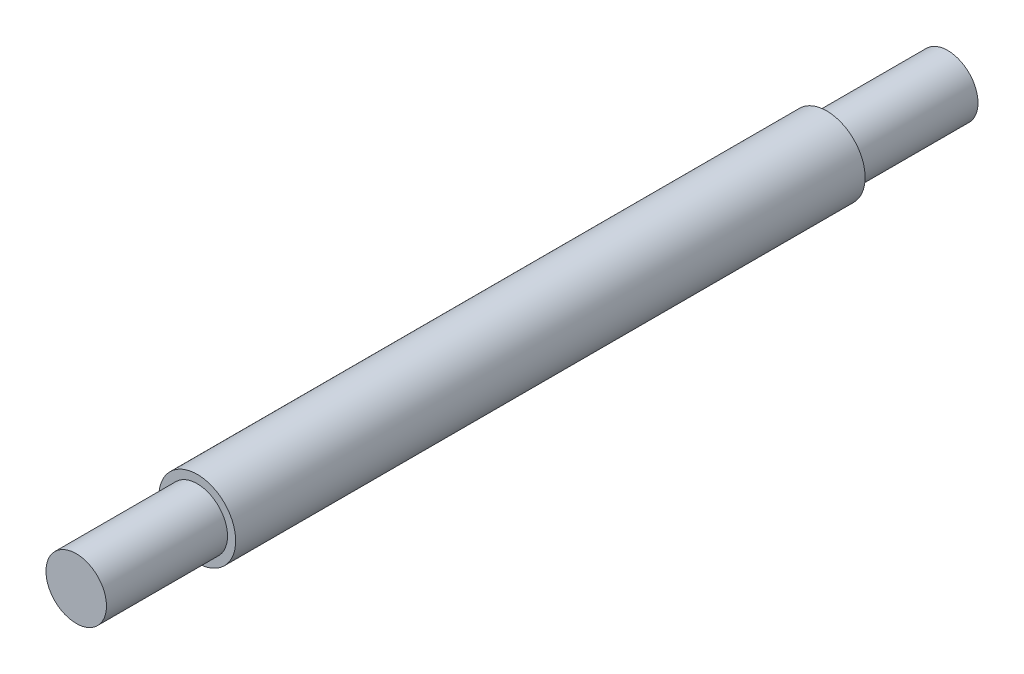
SolidWorks part; units mm, degrees
material "Bordo"
ref_plane "Plano frontal" through (0, 0, 0) normal (0, 0, 1) x (1, 0, 0)
ref_plane "Plano superior" through (0, 0, 0) normal (0, 1, 0) x (1, 0, 0)
ref_plane "Plano direito" through (0, 0, 0) normal (1, 0, 0) x (0, 0, -1)
sketch "Esboço1" plane through (0, 0, 0) normal (0, 0, 1) x (1, 0, 0)
  circle A0 centre (0, 0) radius 2.5
  dimension "D1" = 5
extrude "Ressalto-extrusão1" add sketch "Esboço1" along normal blind 10
sketch "Esboço2" plane through (0, 0, 10) normal (0, 0, 1) x (1, 0, 0)
  circle A0 centre (0, 0) radius 3.175
  dimension "D1" = 6.35
extrude "Ressalto-extrusão2" add sketch "Esboço2" along normal blind 52
sketch "Esboço3" plane through (0, 0, 62) normal (0, 0, 1) x (1, 0, 0)
  circle A0 centre (0, 0) radius 2.5
  dimension "D1" = 5
extrude "Ressalto-extrusão3" add sketch "Esboço3" along normal blind 10
